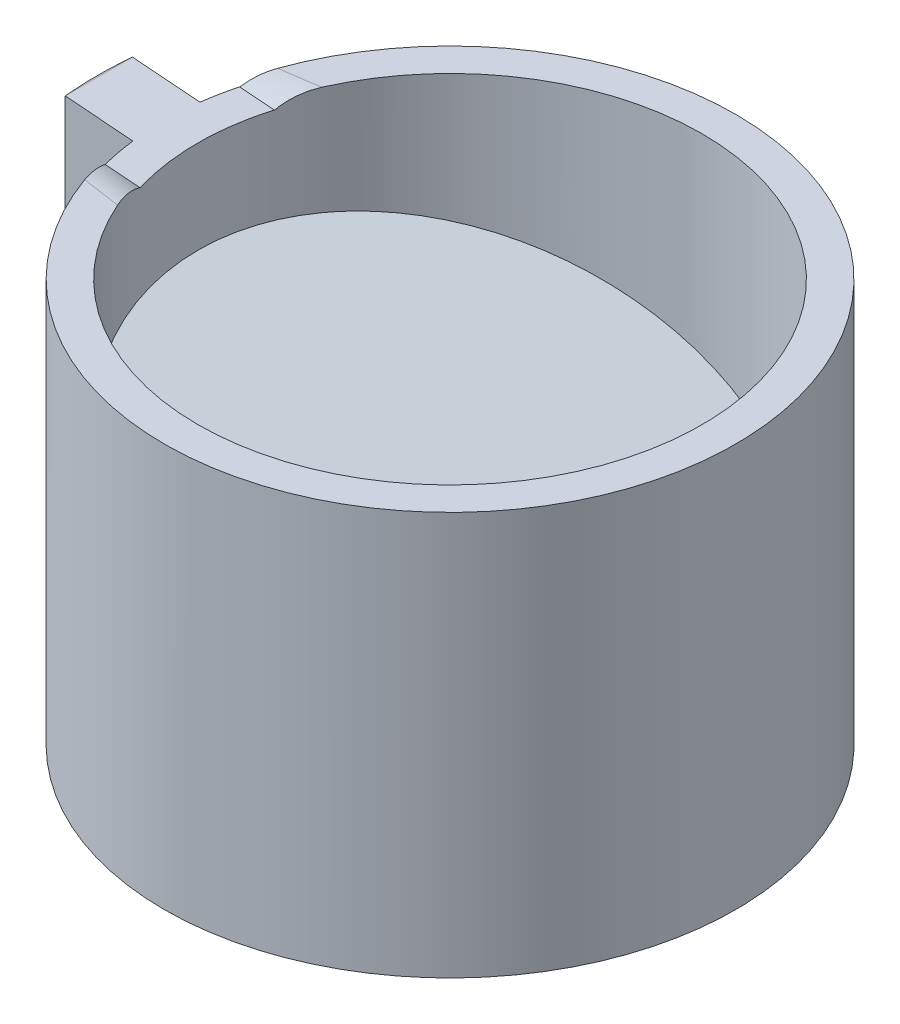
SolidWorks part; units mm, degrees
ref_plane "Front Plane" through (0, 0, 0) normal (0, 0, 1) x (1, 0, 0)
ref_plane "Top Plane" through (0, 0, 0) normal (0, 1, 0) x (1, 0, 0)
ref_plane "Right Plane" through (0, 0, 0) normal (1, 0, 0) x (0, 0, -1)
sketch "Sketch1" plane through (0, 0, 0) normal (0, 1, 0) x (1, 0, 0)
  circle A0 centre (0, 0) radius 9.525
  circle A1 centre (0, 0) radius 10.795
  dimension "D1" = 19.05
  dimension "D2" = 1.27
extrude "Boss-Extrude1" add sketch "Sketch1" along normal blind 2.54 contours A1
sketch "Sketch2" plane through (0, 2.54, 0) normal (0, 1, 0) x (1, 0, 0)
  circle A0 centre (0, 0) radius 9.525
  circle A1 centre (0, 0) radius 10.795
  circle A2 centre (0, 0) radius 10.795 construction
  dimension "D1" = 19.05
extrude "Boss-Extrude2" add sketch "Sketch2" along normal blind 12.7
ref_plane "Plane1" through (0, 12.7, 0) normal (0, 1, 0) x (1, 0, 0)
sketch "Sketch3" plane through (0, 0, 0) normal (0, 0, 1) x (1, 0, 0)
  line L1 (9.525, 2.54) -> (-9.525, 2.54) construction
  line L2 (-9.525, 11.43) -> (-9.525, 2.54)
  line L3 (-9.525, 2.54) -> (9.525, 2.54)
  line L4 (-9.525, 11.43) -> (9.525, 4.5134)
  line L5 (9.525, 4.5134) -> (9.525, 2.54)
  point P4 (0, 0)
  dimension "D1" = 8.89
  dimension "D2" = 1.9734
extrude "Boss-Extrude3" add sketch "Sketch3" along normal mid plane 19.05 contours L2 L3 L5 L4
sketch "Sketch4" plane through (0, 15.24, 0) normal (0, 1, 0) x (1, 0, 0)
  circle A0 centre (0, 0) radius 10.795
  circle A1 centre (0, 0) radius 13.4704
  circle A2 centre (0, 0) radius 10.795 construction
extrude "Cut-Extrude1" cut sketch "Sketch4" against normal up to surface (15.24 mm away) up to face at (0, 0, 10.795)
sketch "Sketch5" plane through (0, 15.24, 0) normal (0, 1, 0) x (1, 0, 0)
  line L0 (0, 0) -> (-16.3634, 0) construction
  line L2 (-9.525, 1.27) -> (-13.2744, 1.27)
  line L3 (-9.525, 1.27) -> (-9.525, -1.27)
  line L4 (-9.525, -1.27) -> (-13.2744, -1.27)
  arc A0 (-13.2744, 1.27) -> (-13.2744, -1.27) centre (0, 0) ccw
  circle A1 centre (0, 0) radius 10.795 construction
  dimension "D1" = 2.54
  dimension "D2" = 1.27
  dimension "D3" = 1.27
  dimension "D4" = 9.525
extrude "Boss-Extrude4" add sketch "Sketch5" against normal blind 5.08
sketch "Sketch7" plane through (0, 0, -1.27) normal (0, 0, -1) x (-1, 0, 0)
  line L0 (13.2744, 13.6281) -> (13.2744, 15.24)
  line L2 (13.2744, 15.24) -> (8.9498, 14.8981)
  line L6 (10.72, 15.24) -> (13.2744, 15.24) construction
  line L7 (13.2744, 10.16) -> (13.2744, 15.24) construction
  line L9 (13.2744, 15.24) -> (8.9801, 16.51)
  line L14 (8.9801, 16.51) -> (8.9498, 14.8981)
  dimension "D1" = 1.6119
  dimension "D2" = 0
  dimension "D3" = 0
  dimension "D4" = 1.6119
extrude "Cut-Extrude6" cut sketch "Sketch7" against normal blind 3.81 and the other way blind 1.27 contours L2 L14 L9
fillet "Fillet1" radius 2.54 2 edges at (-9.836, 15.24, -2.54) (-9.836, 15.24, 2.54)
